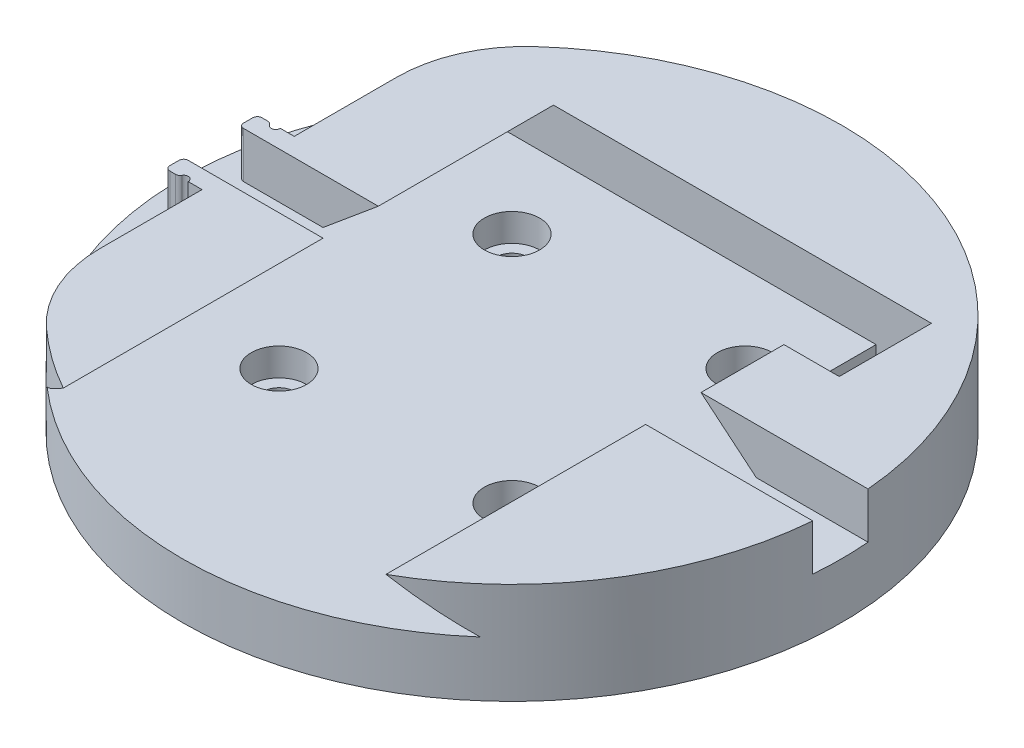
SolidWorks part; units mm, degrees
ref_plane "前视基准面" through (0, 0, 0) normal (0, 0, 1) x (1, 0, 0)
ref_plane "上视基准面" through (0, 0, 0) normal (0, 1, 0) x (1, 0, 0)
ref_plane "右视基准面" through (0, 0, 0) normal (1, 0, 0) x (0, 0, -1)
other "Configuration Table"
sketch "Sketch1" plane through (0, 0, 0) normal (0, 1, 0) x (1, 0, 0)
  line L0 (0, 0) -> (0, 35.75)
  line L1 (0, 0) -> (25.2791, 25.2791)
  line L2 (0, 0) -> (35.75, 0)
  circle A0 centre (0, 0) radius 35.75
  circle A1 centre (12.6395, 12.6395) radius 1.7
  circle A2 centre (12.6395, -12.6395) radius 1.7
  circle A3 centre (-12.6395, -12.6395) radius 1.7
  circle A4 centre (-12.6395, 12.6395) radius 1.7
  dimension "D1" = 71.5
  dimension "D3" = 3.4
  dimension "D2" = 45
extrude "Boss-Extrude1" add sketch "Sketch1" along normal blind 11 contours L0 A0 L2 A2 A3 A4 | A1 L1 A0 L0 | A1 L1 L2 A0 region at (-5.0653, 0, 5.0653) region at (8.8584, 0, -21.5334) region at (21.5334, 0, -8.8584)
sketch "Sketch2" plane through (0, 11, 0) normal (0, 1, 0) x (1, 0, 0)
  line L0 (0, 0) -> (0, 29.8733)
  line L1 (0, 0) -> (21.7146, 0)
  circle A0 centre (12.6395, 12.6395) radius 3
  circle A1 centre (12.6395, -12.6395) radius 3
  circle A2 centre (-12.6395, -12.6395) radius 3
  circle A3 centre (-12.6395, 12.6395) radius 3
  circle M5 centre (12.6395, 12.6395) radius 1.7
  circle M7 centre (12.6395, -12.6395) radius 1.7
  circle M8 centre (-12.6395, -12.6395) radius 1.7
  circle M9 centre (-12.6395, 12.6395) radius 1.7
  dimension "D1" = 6
extrude "Cut-Extrude1" cut sketch "Sketch2" against normal blind 8 contours A2 M8 | A1 M7 | A0 M5 | A3 M9 region at (9.7244, 11, -12.6395) region at (9.7244, 11, 12.6395) region at (-15.5547, 11, 12.6395) region at (-15.5547, 11, -12.6395)
sketch "Sketch3" plane through (0, 11, 0) normal (0, 1, 0) x (1, 0, 0)
  line L0 (0, 0) -> (17.5, 0)
  line L1 (17.5, 0) -> (17.5, 12)
  line L2 (17.5, 12) -> (23.5, 12)
  line L3 (23.5, 12) -> (23.5, 22)
  line L4 (23.5, 22) -> (17.5, 22)
  line L5 (17.5, 22) -> (17.5, 12)
  dimension "D1" = 17.5
  dimension "D2" = 12
  dimension "D3" = 10
  dimension "D4" = 6
extrude "Cut-Extrude2" cut sketch "Sketch3" against normal blind 34 contours L4 L5 L2 L3 region at (20.5, 11, -17)
sketch "Sketch4" plane through (0, 0, 0) normal (0, 0, 1) x (1, 0, 0)
  line L0 (0, 0) -> (0, 6)
  line L1 (-17.5, 6) -> (17.5, 6)
  line L2 (17.5, 6) -> (17.5, 11)
  line L3 (17.5, 11) -> (23.5, 6)
  line L4 (23.5, 6) -> (17.5, 6)
  line L5 (-17.5, 6) -> (-17.5, 11)
  line L6 (-23.5, 6) -> (-17.5, 6)
  line L7 (-17.5, 11) -> (-23.5, 6)
  line L8 (-17.5, 11) -> (17.5, 11)
  dimension "D1" = 6
  dimension "D2" = 17.5
  dimension "D3" = 5
  dimension "D4" = 6
extrude "Cut-Extrude3" cut sketch "Sketch4" against normal up to surface (22 mm away) and the other way blind 44 contours L8 L5 L1 L2 | L5 L7 L6 | L4 L3 L2 region at (0, 8.5, 0) region at (-19.5, 7.6667, 0) region at (19.5, 7.6667, 0) up to face at (20.5, 5.5, -22)
sketch "Sketch5" plane through (23.5, 0, 0) normal (-1, 0, 0) x (0, 0, 1)
  line L0 (0, 0) -> (0, 6)
  line L1 (0, 6) -> (3, 6)
  line L2 (3, 6) -> (3, 11)
  line L3 (31.1739, 11) -> (-35.75, 11) construction
  line L4 (3, 11) -> (-3, 11)
  line L5 (-3, 11) -> (-3, 6)
  line L6 (-3, 6) -> (0, 6)
  dimension "D1" = 3
  dimension "D2" = 3
  dimension "D3" = 6
extrude "Cut-Extrude4" cut sketch "Sketch5" against normal through all and the other way through all contours L5 L6 L1 L2 L4 region at (23.5, 8.5, 0)
sketch "Sketch6" plane through (0, 11, 0) normal (0, 1, 0) x (1, 0, 0)
  line L0 (-35.6239, 3) -> (-32.6239, 3)
  line L1 (-32.6239, -21.1747) -> (-35.6239, -21.1747)
  line L2 (-17.5, 3) -> (-35.6239, 3) construction
  line L3 (-32.6239, 3) -> (-32.6239, 21.1747)
  line L4 (-32.6239, 21.1747) -> (-35.6239, 21.1747)
  line L5 (-35.6239, 21.1747) -> (-35.6239, 3)
  line L6 (-32.6239, 3) -> (-32.6239, 5)
  line L7 (-32.6239, 5) -> (-28.6239, 5)
  line L8 (-28.6239, 5) -> (-28.6239, 31.4033)
  line L9 (-28.6239, 31.4033) -> (-35.6239, 31.4033)
  line L10 (-35.6239, 31.4033) -> (-35.6239, 21.1747)
  line L11 (0, 0) -> (-16.5597, 0)
  line L12 (-35.6239, -31.4033) -> (-35.6239, -21.1747)
  line L13 (-28.6239, -31.4033) -> (-35.6239, -31.4033)
  line L14 (-28.6239, -5) -> (-28.6239, -31.4033)
  line L15 (-35.6239, -21.1747) -> (-35.6239, -3)
  line L16 (-32.6239, -3) -> (-32.6239, -21.1747)
  line L17 (-32.6239, -5) -> (-28.6239, -5)
  line L18 (-35.6239, -3) -> (-32.6239, -3)
  line L19 (-28.6239, 5) -> (-28.6239, 18.959)
  circle A0 centre (-30.6239, 5) radius 0.5
  circle A1 centre (-30.6239, -5) radius 0.5
  arc M16 (-35.6239, -3) -> (-17.5, -31.1739) centre (0, 0) ccw
  dimension "D4" = 2
  dimension "D1" = 3
  dimension "D2" = 4
  dimension "D3" = 2
extrude "Cut-Extrude5" cut sketch "Sketch6" against normal up to surface (5 mm away) contours A0 L7 L8 L9 L10 L4 L3 | L4 L5 L0 L3 | L7 A0 | L7 A0 | A1 L17 | A1 L17 | L17 A1 L16 L14 M16 | L16 L15 L1 M16 | L15 L18 L16 L1 region at (-34.1239, 11, -12.0874) region at (-31.4142, 11, -20.0652) region at (-30.6239, 11, -5.2122) region at (-30.6239, 11, -4.7878) region at (-34.3636, 11, 15.2357) region at (-30.454, 11, 11.8445) region at (-30.6239, 11, 4.7878) region at (-30.6239, 11, 5.2122) up to face at (2.5, 6, -0.3792)
fillet "Fillet3" radius 0.5 6 edges at (-31.1239, 8.5, -5) (-31.1239, 8.5, 5) (-32.6239, 8.5, 5) (-32.6239, 8.5, 3) (-32.6239, 8.5, -3) (-32.6239, 8.5, -5)
fillet "Fillet4" radius 14 2 edges at (-28.6239, 8.5, 21.4181) (-28.6239, 8.5, -21.4181)
